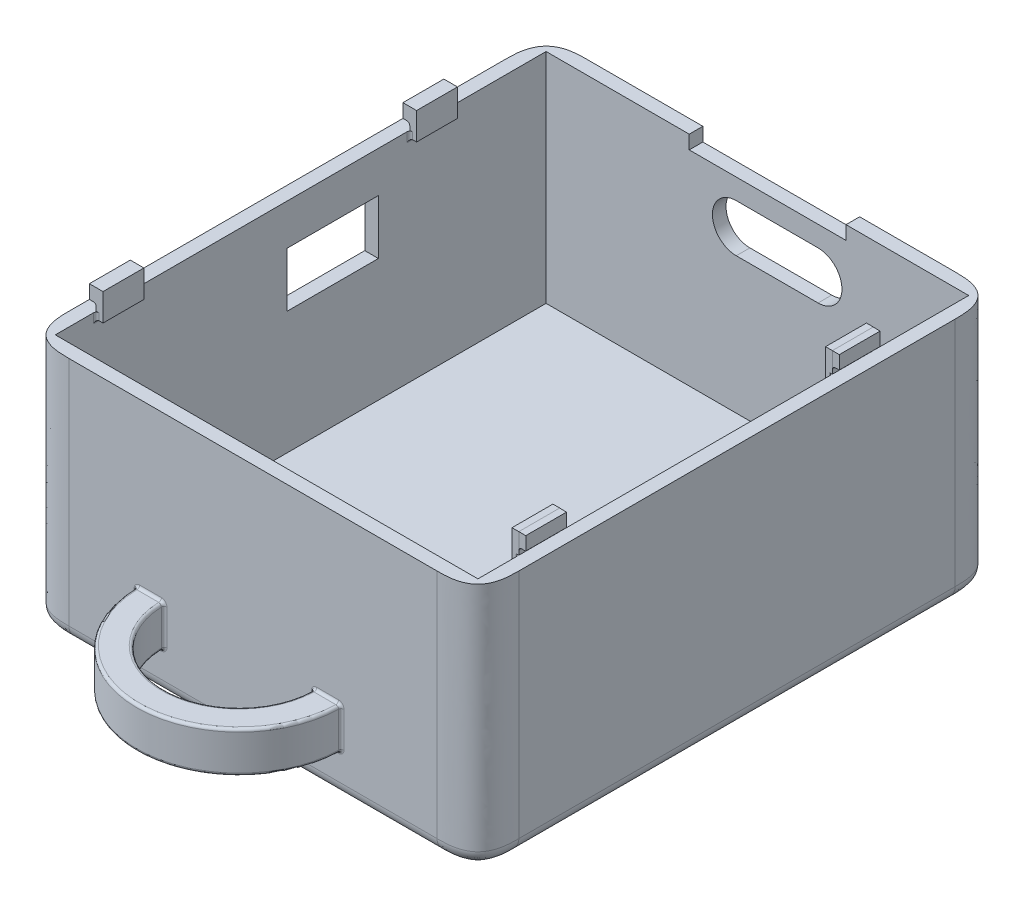
SolidWorks part; units mm, degrees
ref_plane "Front Plane" through (0, 0, 0) normal (0, 0, 1) x (1, 0, 0)
ref_plane "Top Plane" through (0, 0, 0) normal (0, 1, 0) x (1, 0, 0)
ref_plane "Right Plane" through (0, 0, 0) normal (1, 0, 0) x (0, 0, -1)
sketch "Sketch1" plane through (0, 0, 0) normal (0, 1, 0) x (1, 0, 0)
  line L1 (-148.5843, 96.7753) -> (-115.5843, 96.7753)
  line L2 (-148.5843, 96.7753) -> (-148.5843, 58.7753)
  line L3 (-148.5843, 58.7753) -> (-115.5843, 58.7753)
  line L4 (-115.5843, 96.7753) -> (-115.5843, 58.7753)
  dimension "D1" = 33
  dimension "D2" = 38
extrude "Bottom-Extrude" add sketch "Sketch1" along normal blind 18
fillet "Sid_Corner-Fillet" radius 3 4 edges at (-115.5843, 9, -58.7753) (-148.5843, 9, -58.7753) (-115.5843, 9, -96.7753) (-148.5843, 9, -96.7753) curvature continuous yes
fillet "Bottom-Fillet" radius 1 8 edges
sketch "Sketch2" plane through (0, 18, 0) normal (0, 1, 0) x (1, 0, 0)
  line L0 (-118.5843, 96.7753) -> (-145.5843, 96.7753) construction
  line L1 (-147.5843, 95.7753) -> (-116.5843, 95.7753)
  line L2 (-147.5843, 95.7753) -> (-147.5843, 59.7753)
  line L3 (-147.5843, 59.7753) -> (-116.5843, 59.7753)
  line L4 (-116.5843, 95.7753) -> (-116.5843, 59.7753)
  line L5 (-145.5843, 58.7753) -> (-118.5843, 58.7753) construction
  line L6 (-148.5843, 93.7753) -> (-148.5843, 61.7753) construction
  line L7 (-115.5843, 61.7753) -> (-115.5843, 93.7753) construction
  dimension "D1" = 1
  dimension "D2" = 1
  dimension "D3" = 1
  dimension "D4" = 1
extrude "Cut-Extrude1" cut sketch "Sketch2" against normal blind 16
ref_plane "Plane7" through (0, 0, -58.7753) normal (0, 0, 1) x (1, 0, 0)
ref_plane "Plane8" through (0, 1, 0) normal (0, 1, 0) x (1, 0, 0)
ref_plane "Plane9" through (0, 3, 0) normal (0, -1, 0) x (-1, 0, 0)
sketch "Sketch21" plane through (0, 3, 0) normal (0, -1, 0) x (-1, 0, 0)
  line L0 (-7.8811, 58.7753) -> (7.8811, 58.7753) construction
  line L2 (140.6031, 58.7753) -> (125.6031, 58.7753)
  arc A0 (125.6031, 58.7753) -> (140.6031, 58.7753) centre (133.1031, 58.7753) ccw
  arc A1 (127.9342, 60.6549) -> (138.2719, 60.6549) centre (133.1031, 58.7753) ccw
  dimension "D1" = 15
  dimension "D2" = 2
  dimension "D3" = 5.5
extrude "Boss-Extrude1" add sketch "Sketch21" against normal blind 3 contours A1 A0 region at (-133.1031, 3, -51.443)
fillet "Fillet1" radius 0.2 12 edges at (-138.6031, 4.5, -58.7753) (-127.6031, 4.5, -58.7753) (-126.6031, 6, -58.7753) (-139.6031, 6, -58.7753) (-133.1031, 6, -53.2753) (-140.6031, 4.5, -58.7753) (-133.1031, 6, -51.2753) (-125.6031, 4.5, -58.7753) (-139.6031, 3, -58.7753) (-133.1031, 3, -51.2753) (-126.6031, 3, -58.7753) (-133.1031, 3, -53.2753)
sketch "Sketch22" plane through (0, 0, -96.7753) normal (0, 0, -1) x (-1, 0, 0)
  line L0 (127.6343, 13.75) -> (133.6343, 13.75) construction
  line L1 (127.6343, 15.5) -> (133.6343, 15.5)
  line L2 (127.6343, 12) -> (133.6343, 12)
  line L3 (118.5843, 18) -> (118.5843, 1) construction
  line L5 (145.5843, 1) -> (145.5843, 18) construction
  line L6 (118.5843, 18) -> (145.5843, 18) construction
  line L8 (125.5843, 18) -> (137.0843, 18)
  line L9 (125.5843, 18) -> (125.5843, 17)
  line L10 (125.5843, 17) -> (137.0843, 17)
  line L11 (137.0843, 18) -> (137.0843, 17)
  arc A0 (127.6343, 15.5) -> (127.6343, 12) centre (127.6343, 13.75) ccw
  arc A1 (133.6343, 12) -> (133.6343, 15.5) centre (133.6343, 13.75) ccw
  point P2 (130.6343, 13.75)
  dimension "D1" = 6
  dimension "D3" = 9.05
  dimension "D4" = 2.5
  dimension "D5" = 11.95
  dimension "D2" = 3.5
  dimension "D6" = 11.5
  dimension "D7" = 7
  dimension "D8" = 1
  dimension "D9" = 1.5
extrude "Cut-USB" cut sketch "Sketch22" against normal up to next
sketch "Sketch23" plane through (-148.5843, 0, 0) normal (-1, 0, 0) x (0, 0, 1)
  line L0 (-61.7753, 1) -> (-61.7753, 18) construction
  line L1 (-83.4753, 15) -> (-76.7753, 15)
  line L2 (-83.4753, 15) -> (-83.4753, 11)
  line L3 (-83.4753, 11) -> (-76.7753, 11)
  line L4 (-76.7753, 15) -> (-76.7753, 11)
  line L5 (-93.7753, 18) -> (-61.7753, 18) construction
  dimension "D1" = 4
  dimension "D2" = 6.7
  dimension "D3" = 15
  dimension "D4" = 3
extrude "Cut-BT" cut sketch "Sketch23" against normal up to surface (1 mm away) up to face at (-147.5843, 10, -77.7753)
sketch "Sketch24" plane through (-116.5843, 0, 0) normal (-1, 0, 0) x (0, 0, 1)
  line L0 (-59.7753, 18) -> (-95.7753, 18) construction
  line L1 (-65.7753, 19.5) -> (-62.7753, 19.5)
  line L2 (-65.7753, 19.5) -> (-65.7753, 17.5)
  line L3 (-65.7753, 17.5) -> (-62.7753, 17.5)
  line L4 (-62.7753, 19.5) -> (-62.7753, 17.5)
  line L5 (-59.7753, 2) -> (-59.7753, 18) construction
  dimension "D1" = 3
  dimension "D2" = 2
  dimension "D3" = 0.5
  dimension "D4" = 3
extrude "Boss-Clip" add sketch "Sketch24" along normal blind 0.5
sketch "Sketch26" plane through (-116.5843, 0, 0) normal (1, 0, 0) x (0, 0, -1)
  line L0 (62.7753, 18) -> (62.7753, 19.5) construction
  line L1 (62.7753, 19.5) -> (65.7753, 19.5)
  line L2 (62.7753, 19.5) -> (62.7753, 18.5)
  line L3 (62.7753, 18.5) -> (65.7753, 18.5)
  line L4 (65.7753, 19.5) -> (65.7753, 18.5)
  line L5 (65.7753, 19.5) -> (65.7753, 18) construction
  line L6 (62.7753, 19.5) -> (65.7753, 19.5) construction
  dimension "D1" = 3
  dimension "D2" = 1
  dimension "D3" = 0
extrude "Boss-ClipExt" add sketch "Sketch26" along normal blind 0.5 draft 1
fillet "Fillet2" radius 0.2 4 edges at (-116.5843, 17.75, -65.7753) (-116.5843, 17.75, -62.7753) (-116.5843, 17.5, -64.2753) (-116.5843, 18.5, -64.2753)
pattern_linear "LPattern2" count 2 spacing 23 along (0, 0, -1) of "Boss-Clip", "Boss-ClipExt", "Fillet2"
sketch "Sketch27" plane through (-147.5843, 0, 0) normal (1, 0, 0) x (0, 0, -1)
  line L0 (95.7753, 18) -> (59.7753, 18) construction
  line L1 (62.7753, 19.5) -> (65.7753, 19.5)
  line L2 (62.7753, 19.5) -> (62.7753, 17.5)
  line L3 (62.7753, 17.5) -> (65.7753, 17.5)
  line L4 (65.7753, 19.5) -> (65.7753, 17.5)
  line L5 (59.7753, 2) -> (59.7753, 18) construction
  dimension "D1" = 3
  dimension "D2" = 2
  dimension "D3" = 0.5
  dimension "D4" = 3
extrude "Boss-Clip1" add sketch "Sketch27" along normal blind 0.5
sketch "Sketch28" plane through (-147.5843, 0, 0) normal (-1, 0, 0) x (0, 0, 1)
  line L0 (-62.7753, 19.5) -> (-62.7753, 18) construction
  line L1 (-65.7753, 19.5) -> (-62.7753, 19.5)
  line L2 (-65.7753, 19.5) -> (-65.7753, 18.5)
  line L3 (-65.7753, 18.5) -> (-62.7753, 18.5)
  line L4 (-62.7753, 19.5) -> (-62.7753, 18.5)
  dimension "D1" = 1
  dimension "D2" = 0
extrude "Boss-ClipExt1" add sketch "Sketch28" along normal blind 0.5
fillet "Fillet4" radius 0.2 4 edges at (-147.5843, 18.5, -64.2753) (-147.5843, 17.75, -65.7753) (-147.5843, 17.5, -64.2753) (-147.5843, 17.75, -62.7753)
pattern_linear "LPattern4" count 2 spacing 23 along (0, 0, -1) of "Boss-Clip1", "Boss-ClipExt1", "Fillet4"
